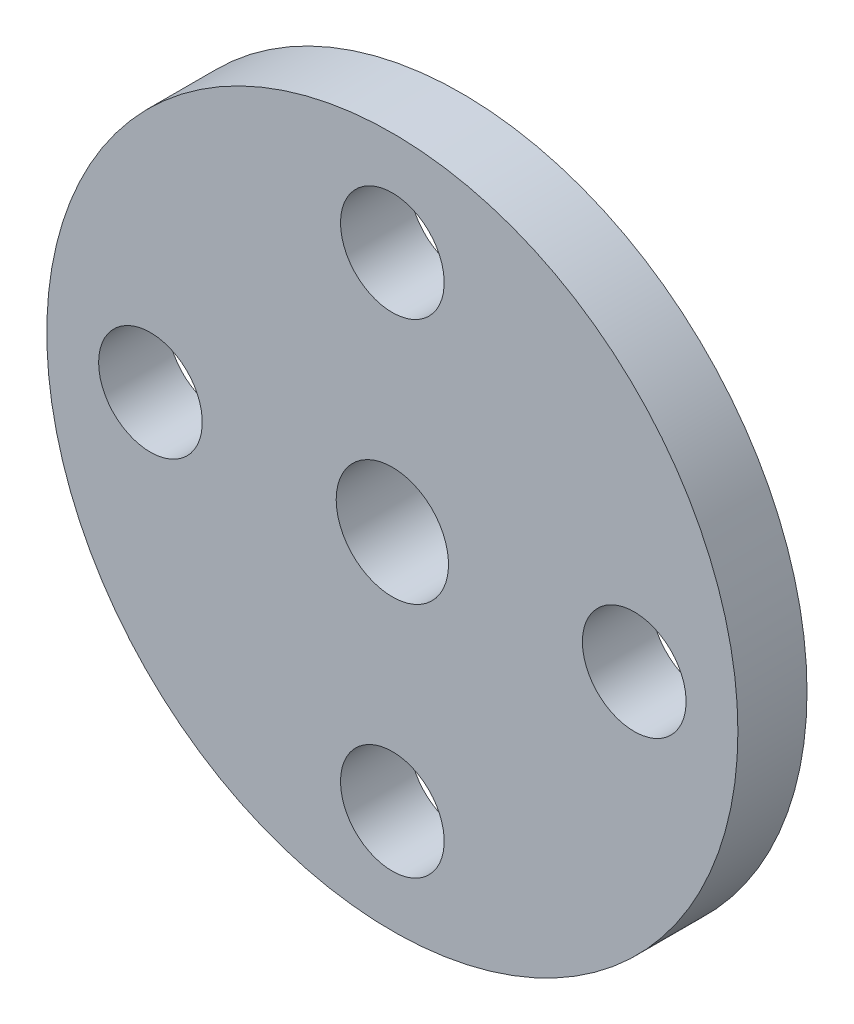
SolidWorks part; units mm, degrees
ref_plane "Piano frontale" through (0, 0, 0) normal (0, 0, 1) x (1, 0, 0)
ref_plane "Piano superiore" through (0, 0, 0) normal (0, 1, 0) x (1, 0, 0)
ref_plane "Piano destro" through (0, 0, 0) normal (1, 0, 0) x (0, 0, -1)
sketch "Schizzo1" plane through (0, 0, 0) normal (0, 0, 1) x (1, 0, 0)
  line L0 (0, 10) -> (0, -10) construction
  line L1 (0, -10) -> (-10, 0) construction
  line L2 (-10, 0) -> (10, 0) construction
  circle A0 centre (0, 0) radius 10
  dimension "D1" = 20
extrude "Estrusione-Estrusione2" add sketch "Schizzo1" along normal blind 2
hole_wizard "Foro Ø3.0 (3)-1" positions "Schizzo3D14" profile "Schizzo2" hole size "Ø3.0" standard "ISO" end condition through all
sketch3d "Schizzo3D14"
  point P0 (7, 0, 0)
  point P2 (-7, 0, 0)
  point P4 (0, -7, 0)
  point P6 (0, 7, 0)
  dimension "D1" = 7
  dimension "D2" = 7
  dimension "D3" = 7
  dimension "D4" = 7
sketch "Schizzo2" plane through (7, 0, 0) normal (1, 0, 0) x (0, 1, 0)
  line L0 (0, 0) -> (0, 2)
  line L1 (0, 2) -> (1.5, 2)
  line L2 (1.5, 2) -> (1.5, 0)
  line L5 (1.5, 0) -> (0, 0)
  line L11 (0, -6.35) -> (0, 107.95) construction
  dimension "Thru Hole Dia." = 3
  dimension "Thru Hole Depth" = 2
cosmetic thread "Filettatura cosmetica2" parameters "D1"=1.9999, "D2"=3
cosmetic thread "Filettatura cosmetica3" parameters "D1"=1.9999, "D2"=3
cosmetic thread "Filettatura cosmetica4" parameters "D1"=1.9999, "D2"=3
cosmetic thread "Filettatura cosmetica5" parameters "D1"=1.9999, "D2"=3
sketch "Schizzo3" plane through (0, 0, 0) normal (0, 0, 1) x (1, 0, 0)
  circle A0 centre (0, 0) radius 4.5
  dimension "D1" = 9
extrude "Estrusione-Estrusione3" add sketch "Schizzo3" against normal blind 2
sketch "Schizzo20" plane through (0, 0, -2) normal (0, 0, -1) x (-1, 0, 0)
  circle A0 centre (0, 0) radius 1.625
  dimension "D1" = 3.25
extrude "Taglio-Estrusione1" cut sketch "Schizzo20" against normal through all
